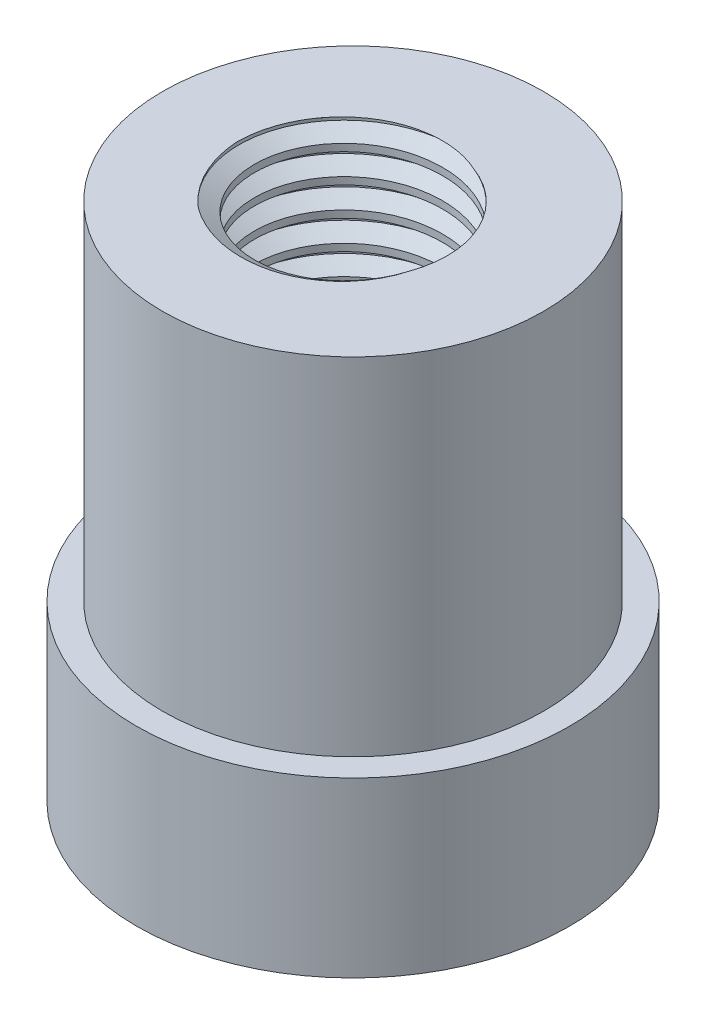
SolidWorks part; units mm, degrees
material "6061-T6 (SS)"
ref_plane "Front Plane" through (0, 0, 0) normal (0, 0, 1) x (1, 0, 0)
ref_plane "Top Plane" through (0, 0, 0) normal (0, 1, 0) x (1, 0, 0)
ref_plane "Right Plane" through (0, 0, 0) normal (1, 0, 0) x (0, 0, -1)
sketch "Sketch1" plane through (0, 0, 0) normal (0, 1, 0) x (1, 0, 0)
  circle A0 centre (0, 0) radius 3.4544
  circle A1 centre (0, 0) radius 6.985
  circle A2 centre (0, 0) radius 7.9375
  dimension "D1" = 15.875
  dimension "D2" = 13.97
  dimension "D3" = 6.9088
extrude "Boss-Extrude1" add sketch "Sketch1" along normal blind 19.05 contours A1 A0 region at (-6.7874, 0, 0)
extrude "Boss-Extrude2" add sketch "Sketch2<3>" along normal blind 6.35 contours A2 A1 region at (-7.713, 0, 0)
sketch "Sketch2<3>" plane through (0, 0, 0) normal (0, 1, 0) x (1, 0, 0) same geometry as "Sketch1"
thread "Thread1" pitch 1.0583 profile "Thread Profile1" start angle 0, offset 1, length 0, pitch 1.0583, diameter 6.9088
ref_plane "Plane1" through (3.4544, -1, 0) normal (0, 0, 1) x (1, 0, 0)
sketch "Thread Profile1" plane through (3.4544, -1, 0) normal (0, 0, 1) x (1, 0, 0)
  line L0 (0, 0) -> (0, 1.0583) construction
  line L1 (0, 0) -> (0.5728, 0.3307)
  line L2 (0.5728, 0.3307) -> (0.5728, 0.463)
  line L3 (0.5728, 0.463) -> (0, 0.7937)
  line L4 (0.5728, 0.3969) -> (0, 0.3969) construction
  line L11 (0, 0) -> (0, 0.7937)
  point P2 (0, 0)
  dimension "Pitch" = 1.0583
  dimension "Profile_Angle" = 60
  dimension "Profile_Land" = 0.1323
  dimension "Profile_Height" = 0.5728
